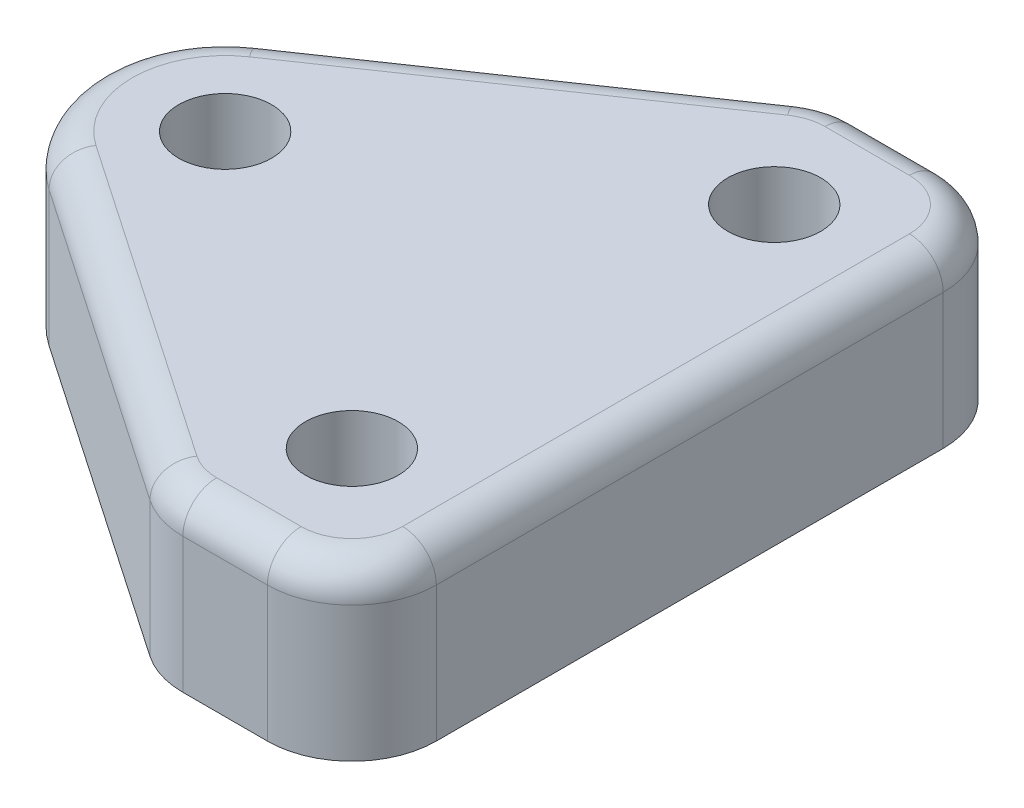
SolidWorks part; units mm, degrees
material "ABS"
ref_plane "Front Plane" through (0, 0, 0) normal (0, 0, 1) x (1, 0, 0)
ref_plane "Top Plane" through (0, 0, 0) normal (0, 1, 0) x (1, 0, 0)
ref_plane "Right Plane" through (0, 0, 0) normal (1, 0, 0) x (0, 0, -1)
ref_axis "X" through (-88.99, 0, 0) along (1, 0, 0)
ref_axis "Y" through (0, 55, 0) along (0, -1, 0)
ref_axis "Z" through (0, 0, -88.99) along (0, 0, 1)
sketch "Sketch1" plane through (0, 0, 0) normal (0, 1, 0) x (1, 0, 0)
  line L0 (0, 0) -> (20, 0) construction
  line L1 (20, 0) -> (20, 12.5) construction
  line L2 (20, 0) -> (20, -12.5) construction
  line L3 (-4.2345, -6.1902) -> (14.677, -19.1268)
  line L4 (17.5, -20) -> (22.5, -20)
  line L5 (27.5, -15) -> (27.5, 15)
  line L6 (22.5, 20) -> (17.5, 20)
  line L7 (14.677, 19.1268) -> (-4.2345, 6.1902)
  line L8 (20, 0) -> (27.5, 0) construction
  line L9 (20, 12.5) -> (20, 20) construction
  line L10 (20, -12.5) -> (20, -20) construction
  circle A0 centre (0, 0) radius 2.5 construction
  circle A1 centre (20, 12.5) radius 2.5 construction
  circle A2 centre (20, -12.5) radius 2.5 construction
  arc A3 (-4.2345, 6.1902) -> (-4.2345, -6.1902) centre (0, 0) ccw
  arc A4 (14.677, -19.1268) -> (17.5, -20) centre (17.5, -15) ccw
  arc A5 (22.5, -20) -> (27.5, -15) centre (22.5, -15) ccw
  arc A6 (27.5, 15) -> (22.5, 20) centre (22.5, 15) ccw
  arc A7 (17.5, 20) -> (14.677, 19.1268) centre (17.5, 15) ccw
  dimension "D1" = 20
  dimension "D2" = 5
  dimension "D3" = 25
  dimension "D4" = 5
  dimension "D7" = 5
  dimension "D5" = 7.5
  dimension "D6" = 40
extrude "Boss-Extrude1" add sketch "Sketch1" along normal blind 10
sketch "Sketch4" plane through (0, 10, 0) normal (0, 1, 0) x (1, 0, 0)
  point P0 (0, 0)
  point P3 (20, 12.5)
  point P6 (20, -12.5)
hole_wizard "M5 Clearance Hole1" positions "Sketch4" profile "Sketch3" hole size "M5" standard "ANSI Metric" end condition through all
sketch "Sketch3" plane through (0, 10, 0) normal (1, 0, 0) x (0, 0, 1)
  line L0 (0, 0) -> (0, 10)
  line L1 (0, 10) -> (2.75, 10)
  line L2 (2.75, 10) -> (2.75, 0)
  line L5 (2.75, 0) -> (0, 0)
  line L11 (0, -6.35) -> (0, 107.95) construction
  dimension "Thru Hole Dia." = 5.5
  dimension "Thru Hole Depth" = 10
fillet "Fillet1" radius 2 10 edges at (5.2213, 10, -12.6585) (16.0225, 10, -19.7767) (20, 10, -20) (26.0355, 10, -18.5355) (27.5, 10, 0) (26.0355, 10, 18.5355) (20, 10, 20) (16.0225, 10, 19.7767) (5.2213, 10, 12.6585) (-7.5, 10, 0)
